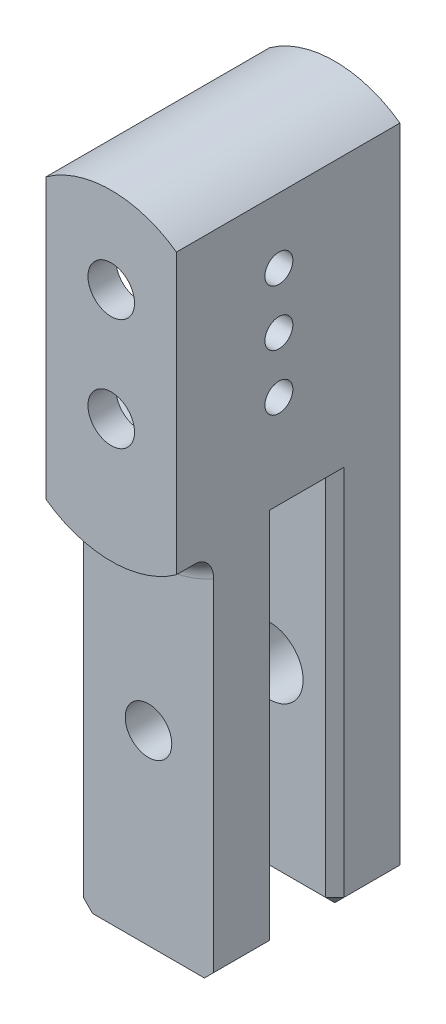
SolidWorks part; units mm, degrees
material "PET"
ref_plane "Front Plane" through (0, 0, 0) normal (0, 0, 1) x (1, 0, 0)
ref_plane "Top Plane" through (0, 0, 0) normal (0, 1, 0) x (1, 0, 0)
ref_plane "Right Plane" through (0, 0, 0) normal (1, 0, 0) x (0, 0, -1)
sketch "Sketch1" plane through (0, 0, 0) normal (0, 0, 1) x (1, 0, 0)
  line L1 (0, 0) -> (7, 0)
  line L2 (0, 0) -> (0, -35)
  line L3 (0, -35) -> (7, -35)
  line L4 (7, 0) -> (7, -35)
extrude "Boss-Extrude1" add sketch "Sketch1" along normal blind 3.5
sketch "Sketch2" plane through (0, 0, 3.5) normal (0, 0, 1) x (1, 0, 0)
  line L0 (0, 0) -> (0, -15)
  line L1 (0, 0) -> (0, -35) construction
  line L2 (0, -15) -> (7, -15)
  line L3 (7, -35) -> (7, 0) construction
  line L4 (7, -15) -> (7, 0)
  line L5 (7, 0) -> (0, 0)
extrude "Boss-Extrude2" add sketch "Sketch2" along normal blind 3
sketch "Sketch3" plane through (0, 0, 6.5) normal (0, 0, 1) x (1, 0, 0)
  line L1 (0, 0) -> (7, 0)
  line L2 (0, 0) -> (0, -35)
  line L3 (0, -35) -> (7, -35)
  line L4 (7, 0) -> (7, -35)
extrude "Boss-Extrude3" add sketch "Sketch3" along normal blind 3.5
sketch "Sketch4" plane through (0, 0, 10) normal (0, 0, 1) x (1, 0, 0)
  line L1 (0, 0) -> (7, 0)
  line L2 (0, 0) -> (0, -15)
  line L3 (0, -15) -> (7, -15)
  line L4 (7, 0) -> (7, -15)
extrude "Boss-Extrude4" add sketch "Sketch4" along normal blind 2
sketch "Sketch5" plane through (0, 0, 0) normal (-1, 0, 0) x (0, 0, 1)
  line L1 (3.5, -2) -> (10.5, -2)
  line L2 (3.5, -2) -> (3.5, -11)
  line L3 (3.5, -11) -> (10.5, -11)
  line L4 (10.5, -2) -> (10.5, -11)
  line L5 (12, 0) -> (0, 0) construction
  line L6 (12, 0) -> (12, -15) construction
  dimension "D1" = 9
  dimension "D2" = 7
  dimension "D3" = 1.5
  dimension "D4" = 2
extrude "Cut-Extrude1" cut sketch "Sketch5" against normal blind 5.5
sketch "Sketch6" plane through (5.5, 0, 0) normal (-1, 0, 0) x (0, 0, 1)
  line L0 (6.5, -2) -> (6.5, -11) construction
  line L1 (10.5, -2) -> (3.5, -2) construction
  line L2 (3.5, -11) -> (10.5, -11) construction
  line L3 (10.5, -11) -> (10.5, -2) construction
  line L4 (10.5, -2) -> (3.5, -2) construction
  circle A0 centre (6.5, -3.5) radius 0.75
  circle A1 centre (6.5, -9.5) radius 0.75
  circle A2 centre (6.5, -6.5) radius 0.75
  dimension "D2" = 1.5
  dimension "D4" = 4.5
  dimension "D1" = 4
  dimension "D3" = 1.5
extrude "Cut-Extrude2" cut sketch "Sketch6" against normal up to next
sketch "Sketch7" plane through (0, 0, 12) normal (0, 0, 1) x (1, 0, 0)
  line L0 (3.5, 0) -> (3.5, -15) construction
  line L1 (7, 0) -> (0, 0) construction
  line L2 (0, -15) -> (7, -15) construction
  line L3 (0, -2) -> (7, -2) construction
  line L4 (7, -15) -> (7, 0) construction
  circle A0 centre (3.5, -3.5) radius 1.25
  circle A1 centre (3.5, -9.5) radius 1.25
  dimension "D2" = 7.5
  dimension "D1" = 1.5
extrude "Cut-Extrude3" cut sketch "Sketch7" against normal up to next
sketch "Sketch9" plane through (0, 0, 12) normal (0, 0, 1) x (1, 0, 0)
  line L0 (0, 0) -> (7, 0)
  arc A0 (7, 0) -> (0, 0) centre (3.5, -4.8734) ccw
extrude "Boss-Extrude5" add sketch "Sketch9" against normal up to surface (12 mm away) up to face at (3.5, -17.5, 0)
sketch "Sketch10" plane through (0, 0, 12) normal (0, 0, 1) x (1, 0, 0)
  line L0 (0, -15) -> (7, -15)
  arc A0 (0, -15) -> (7, -15) centre (3.5, -10.1266) ccw
extrude "Boss-Extrude6" add sketch "Sketch10" against normal up to surface (2 mm away) up to face at (3.5, -25, 10)
chamfer "Chamfer1" distance 0.5 angle 45 12 edges at (0, -25, 3.5) (0, -15, 5) (0, -25, 6.5) (7, -35, 8.25) (0, -35, 8.25) (3.5, -35, 6.5) (0, -35, 1.75) (3.5, -35, 3.5) (7, -35, 1.75) (7, -25, 6.5) (7, -25, 3.5) (7, -15, 5)
sketch "Sketch11" plane through (0, 0, 10) normal (0, 0, 1) x (1, 0, 0)
  line L0 (3.5, -35) -> (3.5, -16.1266) construction
  line L1 (0.5, -35) -> (6.5, -35) construction
  arc A0 (0, -15) -> (7, -15) centre (3.5, -10.1266) ccw construction
  circle A1 centre (3.5, -25) radius 1.25
  dimension "D1" = 10
extrude "Cut-Extrude4" cut sketch "Sketch11" against normal up to next
sketch "Sketch12" plane through (0, 0, 0) normal (0, 0, -1) x (-1, 0, 0)
  line L0 (-3.5, -35) -> (-3.5, -18.8417) construction
  line L1 (-0.5, -35) -> (-6.5, -35) construction
  circle A0 centre (-3.5, -25) radius 1.8
  dimension "D1" = 10
extrude "Cut-Extrude5" cut sketch "Sketch12" against normal up to next
fillet "Fillet1" radius 1 1 edges at (3.5, -16.1266, 10)
